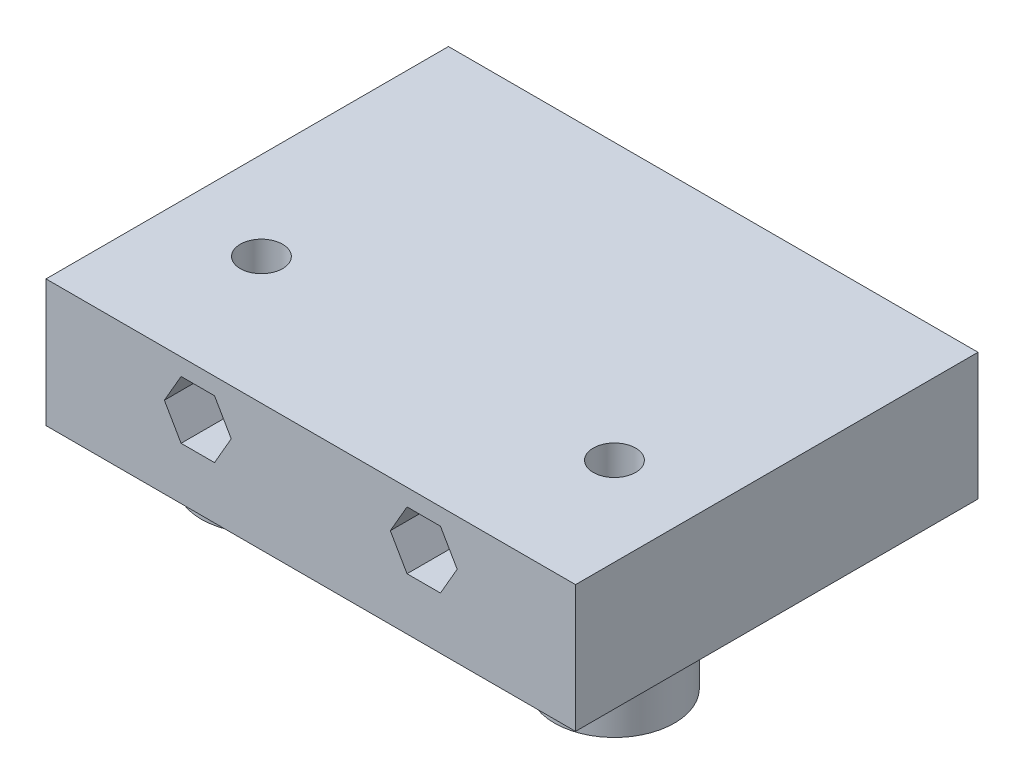
SolidWorks part; units mm, degrees
ref_plane "Front Plane" through (0, 0, 0) normal (0, 0, 1) x (1, 0, 0)
ref_plane "Top Plane" through (0, 0, 0) normal (0, 1, 0) x (1, 0, 0)
ref_plane "Right Plane" through (0, 0, 0) normal (1, 0, 0) x (0, 0, -1)
sketch "Sketch1" plane through (0, 0, 0) normal (0, 0, 1) x (1, 0, 0)
  line L0 (19.1329, -10.6) -> (23.8671, -10.6)
  line L1 (0, 0) -> (75, 0)
  line L2 (0, 0) -> (0, -18)
  line L3 (0, -18) -> (75, -18)
  line L4 (75, 0) -> (75, -18)
  line L9 (23.8671, -10.6) -> (26.2343, -6.5)
  line L10 (26.2343, -6.5) -> (23.8671, -2.4)
  line L15 (23.8671, -2.4) -> (19.1329, -2.4)
  line L16 (19.1329, -2.4) -> (16.7657, -6.5)
  line L17 (16.7657, -6.5) -> (19.1329, -10.6)
  line L18 (19.1329, -10.6) -> (23.8671, -2.4) construction
  line L19 (19.1329, -2.4) -> (23.8671, -10.6) construction
  line L20 (37.5, -18) -> (37.5, 0) construction
  line L21 (58.2343, -6.5) -> (55.8671, -10.6)
  line L22 (55.8671, -2.4) -> (58.2343, -6.5)
  line L23 (51.1329, -2.4) -> (55.8671, -2.4)
  line L24 (48.7657, -6.5) -> (51.1329, -2.4)
  line L25 (51.1329, -10.6) -> (48.7657, -6.5)
  line L26 (55.8671, -2.4) -> (51.1329, -10.6) construction
  line L27 (55.8671, -10.6) -> (51.1329, -2.4) construction
  line L28 (55.8671, -10.6) -> (51.1329, -10.6)
  circle A0 centre (21.5, -6.5) radius 3
  circle A1 centre (53.5, -6.5) radius 3
  point P12 (21.5, -6.5)
  dimension "6" = 6
  dimension "D1" = 18
  dimension "D2" = 75
  dimension "D3" = 32
  dimension "D4" = 11.5
  dimension "D5" = 21.5
  dimension "D7" = 8.2
  dimension "D6" = 8.2
extrude "Boss-Extrude1" add sketch "Sketch1" along normal blind 57 contours L4 L1 L2 L3 L16 L0 L9 region at (37.5, -9.236, 0)
extrude "Boss-Extrude2" add sketch "Sketch1<3>" along normal blind 20 contours L9 L0 A0 | L16 A1 | L16 L17 L0 L9 L10 L15 A0 region at (18.0578, -8.4874, 0) region at (37.5, -9.236, 0) region at (56.9422, -8.4874, 0)
sketch "Sketch1<3>" plane through (0, 0, 0) normal (0, 0, 1) x (1, 0, 0) same geometry as "Sketch1"
sketch "Sketch2" plane through (0, 0, 0) normal (0, 1, 0) x (1, 0, 0)
  line L0 (0, -57) -> (75, -57) construction
  line L1 (0, -57) -> (0, 0) construction
  circle A0 centre (12.5, -38.99) radius 3
  circle A1 centre (62.5, -38.99) radius 3
  circle A2 centre (12.5, -38.99) radius 8.5
  circle A3 centre (62.5, -38.99) radius 8.5
  dimension "D4" = 6
  dimension "D5" = 17
  dimension "D1" = 18.01
  dimension "D2" = 50
  dimension "D3" = 12.5
extrude "Boss-Extrude3" add sketch "Sketch2" against normal blind 10 from surface starting at face at (37.5, -18, 28.5)
extrude "Cut-Extrude3" cut sketch "Sketch2<2>" against normal up to surface (18 mm away) contours A0 | A1 region at (12.5, 0, 38.99) region at (62.5, 0, 38.99) up to face at (12.5, -18, 47.49)
sketch "Sketch2<2>" plane through (0, 0, 0) normal (0, 1, 0) x (1, 0, 0) same geometry as "Sketch2"
sketch "Sketch3" plane through (0, -18, 0) normal (0, -1, 0) x (1, 0, 0)
  line L0 (0, 57) -> (0, 0) construction
  line L1 (16.5, 24.5) -> (26.5, 24.5)
  line L2 (16.5, 24.5) -> (16.5, 19.5)
  line L3 (16.5, 19.5) -> (26.5, 19.5)
  line L4 (26.5, 24.5) -> (26.5, 19.5)
  line L5 (16.5, 24.5) -> (26.5, 19.5) construction
  line L6 (16.5, 19.5) -> (26.5, 24.5) construction
  line L7 (48.5, 24.5) -> (58.5, 24.5)
  line L8 (48.5, 24.5) -> (48.5, 19.5)
  line L9 (48.5, 19.5) -> (58.5, 19.5)
  line L10 (58.5, 24.5) -> (58.5, 19.5)
  line L11 (48.5, 24.5) -> (58.5, 19.5) construction
  line L12 (48.5, 19.5) -> (58.5, 24.5) construction
  line L13 (0, 0) -> (75, 0) construction
  point P0 (21.5, 22)
  point P5 (53.5, 22)
  point P10 (0, 0)
  dimension "D1" = 32
  dimension "D2" = 5
  dimension "D3" = 10
  dimension "D4" = 21.5
  dimension "D5" = 22
extrude "Cut-Extrude4" cut sketch "Sketch3" against normal blind 10
equation "\"D5@Sketch1\"=(\"D2@Sketch1\"-\"D3@Sketch1\")/2"
equation "\"D6@Sketch1\"=\"D7@Sketch1\""
equation "\"D3@Sketch2\"=(75-50)/2"
